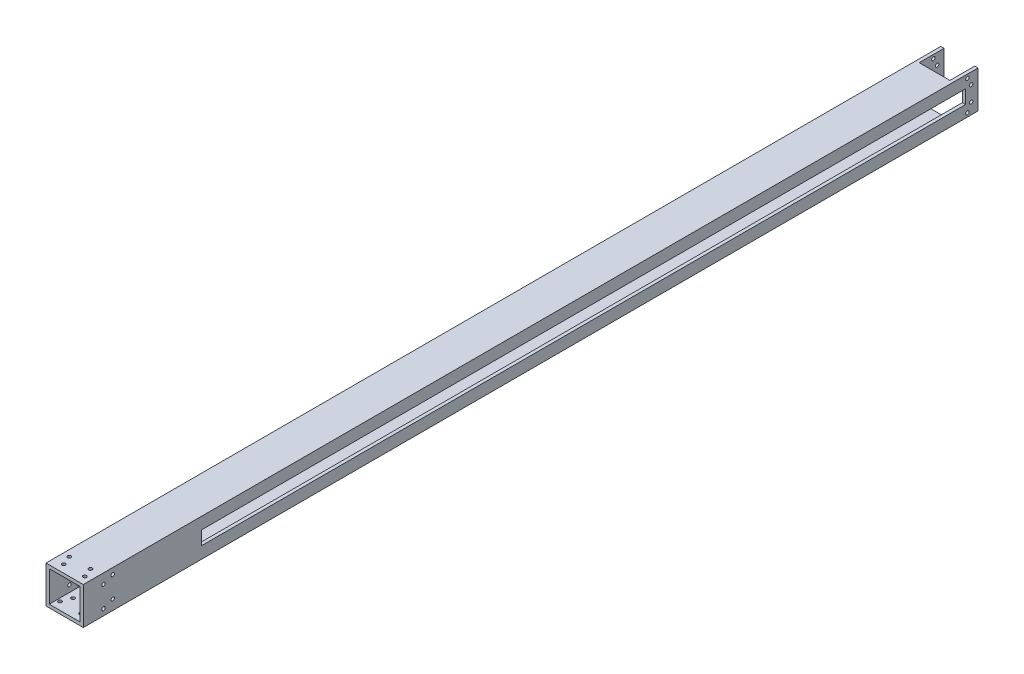
SolidWorks part; units mm, degrees
ref_plane "Front Plane" through (0, 0, 0) normal (1, 0, 0) x (0, 1, 0)
ref_plane "Top Plane" through (0, 0, 0) normal (0, 0, 1) x (0, 1, 0)
ref_plane "Right Plane" through (0, 0, 0) normal (0, 1, 0) x (-1, 0, 0)
sketch "Sketch1" plane through (0, 0, 0) normal (0, 0, 1) x (0, 1, 0)
  line L0 (19.05, -19.05) -> (19.05, 19.05)
  line L1 (19.05, -19.05) -> (-19.05, -19.05)
  line L2 (19.05, -19.05) -> (19.05, 19.05)
  line L3 (19.05, 19.05) -> (-19.05, 19.05)
  line L4 (-19.05, -19.05) -> (-19.05, 19.05)
  line L5 (19.05, -19.05) -> (-19.05, 19.05) construction
  line L6 (19.05, 19.05) -> (-19.05, -19.05) construction
  line L7 (19.05, 19.05) -> (-19.05, 19.05)
  line L8 (-19.05, -19.05) -> (-19.05, 19.05)
  line L9 (19.05, -19.05) -> (-19.05, -19.05)
  line L10 (15.7163, 15.7163) -> (-15.7162, 15.7163)
  line L11 (-15.7162, -15.7163) -> (-15.7162, 15.7163)
  line L12 (15.7163, -15.7162) -> (-15.7162, -15.7163)
  line L13 (15.7163, -15.7162) -> (15.7163, 15.7163)
  line L14 (-6.985, -15.7162) -> (-6.985, -19.05)
  line L15 (6.985, -15.7163) -> (6.985, -19.05)
  line L16 (-15.7162, -15.7163) -> (-6.985, -15.7162)
  line L17 (-6.985, -17.3831) -> (-19.05, -17.3831) construction
  line L18 (6.985, -17.3831) -> (19.05, -17.3831) construction
  point P0 (0, 0)
  dimension "D1" = 38.1
  dimension "D4" = 13.97
  dimension "D3" = 31.4325
  dimension "D2" = 0
extrude "Boss-Extrude1" add sketch "Sketch1" along normal blind 914.4 contours L4 L1 L0 L3 L13 L12 L11 L10 region at (18.5112, 13.0175, 0)
sketch "Sketch6" plane through (0, 0, 0) normal (0, 0, 1) x (0, 1, 0)
  line L1 (26.9875, -26.9875) -> (-26.9875, -26.9875) construction
  line L2 (26.9875, -26.9875) -> (26.9875, 26.9875) construction
  line L3 (26.9875, 26.9875) -> (-26.9875, 26.9875) construction
  line L4 (-26.9875, -26.9875) -> (-26.9875, 26.9875) construction
  line L5 (26.9875, -26.9875) -> (-26.9875, 26.9875) construction
  line L6 (26.9875, 26.9875) -> (-26.9875, -26.9875) construction
  line L11 (-26.9875, 25.8156) -> (-16.9875, 25.8156)
  line L12 (-26.9875, 25.8156) -> (-26.9875, 21.8156)
  line L13 (-26.9875, 21.8156) -> (-16.9875, 21.8156)
  line L14 (-16.9875, 25.8156) -> (-16.9875, 21.8156)
  line L15 (-23.4875, 25.8156) -> (-20.4875, 25.8156)
  line L16 (-23.4875, 25.8156) -> (-23.4875, -2.5726)
  line L17 (-23.4875, -2.5726) -> (-20.4875, -2.5726)
  line L18 (-20.4875, 25.8156) -> (-20.4875, -2.5726)
  point P0 (0, 0)
  point P14 (-21.9875, 25.8156)
  point P15 (-21.9875, 25.8156)
  dimension "D1" = 53.975
  dimension "D2" = 4
  dimension "D3" = 10
  dimension "D4" = 3
sketch "Sketch8" plane through (0, 19.05, 0) normal (0, 1, 0) x (-1, 0, 0)
  line L0 (-19.05, 0) -> (19.05, 0) construction
  line L1 (15.7163, -25.4) -> (-15.7162, -25.4)
  line L2 (15.7163, -25.4) -> (15.7163, 25.4)
  line L3 (15.7163, 25.4) -> (-15.7162, 25.4)
  line L4 (-15.7162, -25.4) -> (-15.7162, 25.4)
  line L5 (15.7163, -25.4) -> (-15.7162, 25.4) construction
  line L6 (15.7163, 25.4) -> (-15.7162, -25.4) construction
  point P0 (0, 0)
  dimension "1.25" = 31.4325
  dimension "D2" = 25.4
extrude "Cut-Extrude3" cut sketch "Sketch8" against normal blind 71.882
ref_axis "Axis1" through (0, 0, 960.12) along (0, 0, -1)
sketch "Sketch11" plane through (19.05, 0, 0) normal (1, 0, 0) x (0, 1, 0)
  line L0 (6.985, 914.4) -> (6.985, 0) construction
  line L1 (-6.985, 0) -> (6.985, 0)
  line L2 (-6.985, 0) -> (-6.985, 12.7)
  line L3 (-6.985, 12.7) -> (6.985, 12.7)
  line L4 (6.985, 0) -> (6.985, 12.7)
  dimension "D1" = 12.7
extrude "Boss-Extrude2" add sketch "Sketch11" against normal up to surface (3.3338 mm away) up to face at (15.7162, -13.9171, 313.2667)
sketch "Sketch9" plane through (19.05, 0, 0) normal (1, 0, 0) x (0, 1, 0)
  line L0 (19.05, 0) -> (-19.05, 0) construction
  line L1 (19.05, 0) -> (-19.05, 0) construction
  line L2 (19.05, 0) -> (-19.05, 0) construction
  line L3 (19.05, 0) -> (-19.05, 0) construction
  line L4 (15.7163, 25.4) -> (19.05, 25.4) construction
  line L6 (15.7163, 25.4) -> (19.05, 25.4) construction
  line L10 (0, 0) -> (0, 6.35) construction
  circle A0 centre (-15.24, 10.795) radius 1.75
  circle A2 centre (15.24, 10.795) radius 1.75
  circle A3 centre (15.24, 10.795) radius 10.541 construction
  circle A5 centre (7.62, 6.985) radius 1.75
  circle A6 centre (-7.62, 6.985) radius 1.75
  point P12 (4.699, 10.795)
  point P15 (-15.24, 10.795)
  dimension "D2" = 3.5
  dimension "D3" = 6.35
  dimension "D5" = 21.082
  dimension "D7" = 7.62
  dimension "D1" = 0
  dimension "D4" = 15.24
  dimension "D6" = 10.795
  dimension "D8" = 3.81
extrude "Cut-Extrude4" cut sketch "Sketch9" against normal blind 68.326
sketch "Sketch12" plane through (19.05, 0, 0) normal (1, 0, 0) x (0, 1, 0)
  line L0 (19.05, 914.4) -> (19.05, 0) construction
  line L1 (-19.05, 914.4) -> (19.05, 914.4)
  line L2 (-19.05, 914.4) -> (-19.05, 793.75)
  line L3 (-19.05, 793.75) -> (19.05, 793.75)
  line L4 (19.05, 914.4) -> (19.05, 793.75)
  dimension "D1" = 781.05
extrude "Boss-Extrude3" add sketch "Sketch12" against normal up to surface (3.3338 mm away) up to face at (15.7163, -13.49, 10.795)
sketch "Sketch13" plane through (19.05, 0, 0) normal (1, 0, 0) x (0, 1, 0)
  line L0 (-8.89, 884.2375) -> (-12.7, 884.2375) construction
  line L1 (-8.89, 884.2375) -> (-8.89, 893.7625) construction
  line L2 (-8.89, 893.7625) -> (-12.7, 893.7625) construction
  line L3 (-12.7, 884.2375) -> (-12.7, 893.7625) construction
  line L4 (-8.89, 884.2375) -> (-12.7, 893.7625) construction
  line L5 (-8.89, 893.7625) -> (-12.7, 884.2375) construction
  line L6 (-19.05, 914.4) -> (-19.05, 0) construction
  line L7 (19.05, 914.4) -> (-19.05, 914.4) construction
  line L8 (19.05, 914.4) -> (19.05, 0) construction
  line L9 (-15.7162, 914.4) -> (-15.7163, 25.4) construction
  line L10 (-15.7162, 914.4) -> (-15.7163, 25.4) construction
  circle A0 centre (-12.7, 893.7625) radius 1.75
  circle A1 centre (-8.89, 884.2375) radius 1.75
  circle A2 centre (8.89, 893.7625) radius 1.75
  circle A3 centre (12.7, 884.2375) radius 1.75
  circle A4 centre (-12.7, 893.7625) radius 3 construction
  point P0 (-10.795, 889)
  point P12 (4.3319, 900.1125)
  point P22 (-5.3701, 901.1024)
  point P23 (-9.382, 900.1125)
  dimension "D1" = 3.5
  dimension "D8" = 6
  dimension "D2" = 6.35
  dimension "D3" = 25.4
  dimension "D4" = 3.81
  dimension "D5" = 9.525
  dimension "D7" = 6.35
  dimension "D6" = 2
extrude "Cut-Extrude5" cut sketch "Sketch13" against normal blind 6.604
pattern_circular "CirPattern1" count 2 over 360 about axis through (0, 0, 960.12) along (0, 0, -1) of "Cut-Extrude5"
sketch "Sketch14" plane through (0, -19.05, 0) normal (0, -1, 0) x (1, 0, 0)
  line L0 (12.7, 896.9375) -> (8.89, 896.9375) construction
  line L1 (12.7, 896.9375) -> (12.7, 906.4625) construction
  line L2 (12.7, 906.4625) -> (8.89, 906.4625) construction
  line L3 (8.89, 896.9375) -> (8.89, 906.4625) construction
  line L4 (12.7, 896.9375) -> (8.89, 906.4625) construction
  line L5 (12.7, 906.4625) -> (8.89, 896.9375) construction
  line L6 (19.05, 914.4) -> (19.05, 0) construction
  line L7 (19.05, 914.4) -> (-19.05, 914.4) construction
  line L8 (0, 914.4) -> (0, 916.8076) construction
  line L9 (-19.05, 914.4) -> (-19.05, 0) construction
  circle A0 centre (8.89, 906.4625) radius 1.75
  circle A1 centre (12.7, 896.9375) radius 1.75
  circle A2 centre (8.89, 906.4625) radius 3 construction
  circle A3 centre (-12.7, 906.4625) radius 1.75
  circle A4 centre (-8.89, 896.9375) radius 1.75
  point P0 (10.795, 901.7)
  point P16 (-8.064, 906.4625)
  dimension "D1" = 3.5
  dimension "D4" = 6
  dimension "D2" = 3.81
  dimension "D3" = 9.525
  dimension "D5" = 6.35
  dimension "D6" = 12.7
  dimension "D8" = 6.35
  dimension "D7" = 2
extrude "Cut-Extrude6" cut sketch "Sketch14" against normal blind 18.796
pattern_circular "CirPattern2" count 2 over 360 about axis through (0, 0, 960.12) along (0, 0, -1) of "Cut-Extrude6"
sketch "Sketch15" plane through (-19.05, 0, 0) normal (-1, 0, 0) x (0, -1, 0)
  line L0 (2.54, 46.0375) -> (-2.54, 46.0375) construction
  line L1 (2.54, 46.0375) -> (2.54, 55.5625) construction
  line L2 (2.54, 55.5625) -> (-2.54, 55.5625) construction
  line L3 (-2.54, 46.0375) -> (-2.54, 55.5625) construction
  line L4 (2.54, 46.0375) -> (-2.54, 55.5625) construction
  line L5 (2.54, 55.5625) -> (-2.54, 46.0375) construction
  line L6 (-19.05, 0) -> (19.05, 0) construction
  circle A0 centre (-2.54, 55.5625) radius 3
  circle A1 centre (2.54, 46.0375) radius 3
  point P0 (0, 50.8)
  point P7 (0, 0)
  dimension "D1" = 6
  dimension "D2" = 9.525
  dimension "D3" = 5.08
  dimension "D4" = 50.8
extrude "Cut-Extrude7" cut sketch "Sketch15" against normal blind 18.796
